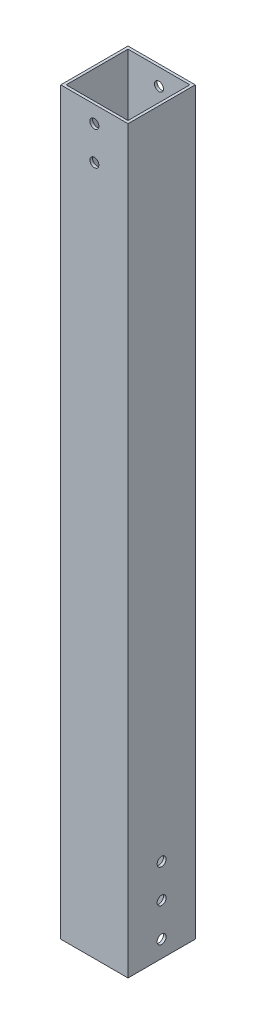
SolidWorks part; units mm, degrees
material "6061 Alloy"
ref_plane "Front Plane" through (0, 0, 0) normal (0, 0, 1) x (1, 0, 0)
ref_plane "Top Plane" through (0, 0, 0) normal (0, 1, 0) x (1, 0, 0)
ref_plane "Right Plane" through (0, 0, 0) normal (1, 0, 0) x (0, 0, -1)
sketch "Sketch1" plane through (0, 0, 0) normal (0, 1, 0) x (1, 0, 0)
  line L1 (19.05, 19.05) -> (-19.05, 19.05)
  line L2 (19.05, 19.05) -> (19.05, -19.05)
  line L3 (19.05, -19.05) -> (-19.05, -19.05)
  line L4 (-19.05, 19.05) -> (-19.05, -19.05)
  line L5 (19.05, 19.05) -> (-19.05, -19.05) construction
  line L6 (19.05, -19.05) -> (-19.05, 19.05) construction
  point P0 (0, 0)
  dimension "D1" = 38.1
extrude "Extrude-Thin1" add sketch "Sketch1" along normal blind 419.1 thin thin type one direction reverse wall 1.524
sketch "Sketch2" plane through (19.05, 0, 0) normal (1, 0, 0) x (0, 0, -1)
  line L0 (-19.05, 0) -> (19.05, 0) construction
  circle A0 centre (0, 9.525) radius 2.54
  circle A1 centre (0, 28.575) radius 2.54
  circle A2 centre (0, 47.625) radius 2.54
  point P7 (0, 0)
  dimension "D1" = 5.08
  dimension "D4" = 19.05
  dimension "D2" = 9.525
  dimension "D3" = 28.575
hole_wizard "#10 Clearance Hole1" positions "Sketch3" profile "Sketch4" hole size "#10" standard "ANSI Inch" end condition through all
sketch "Sketch3" plane through (19.05, 0, 0) normal (1, 0, 0) x (0, 0, -1)
  point P0 (0, 9.525)
  point P3 (0, 28.575)
  point P6 (0, 47.625)
sketch "Sketch4" plane through (19.05, 9.525, 0) normal (0, 1, 0) x (0, 0, -1)
  line L0 (0, 0) -> (0, 38.1)
  line L1 (0, 38.1) -> (2.5527, 38.1)
  line L2 (2.5527, 38.1) -> (2.5527, 0)
  line L5 (2.5527, 0) -> (0, 0)
  line L11 (0, -6.35) -> (0, 107.95) construction
  dimension "Thru Hole Dia." = 5.1054
  dimension "Thru Hole Depth" = 38.1
sketch "Sketch5" plane through (0, 0, 19.05) normal (0, 0, 1) x (1, 0, 0)
  line L0 (-19.05, 419.1) -> (19.05, 419.1) construction
  circle A0 centre (0, 409.575) radius 2.54
  circle A1 centre (0, 390.525) radius 2.54
  point P7 (0, 0)
  point P8 (0, 0)
  dimension "D1" = 5.08
  dimension "D2" = 9.525
  dimension "D3" = 28.575
hole_wizard "#10 Clearance Hole2" positions "Sketch6" profile "Sketch7" hole size "#10" standard "ANSI Inch" end condition through all
sketch "Sketch6" plane through (0, 0, 19.05) normal (0, 0, 1) x (1, 0, 0)
  point P0 (0, 390.525)
  point P3 (0, 409.575)
sketch "Sketch7" plane through (0, 390.525, 19.05) normal (1, 0, 0) x (0, -1, 0)
  line L0 (0, 0) -> (0, 38.1)
  line L1 (0, 38.1) -> (2.5527, 38.1)
  line L2 (2.5527, 38.1) -> (2.5527, 0)
  line L5 (2.5527, 0) -> (0, 0)
  line L11 (0, -6.35) -> (0, 107.95) construction
  dimension "Thru Hole Dia." = 5.1054
  dimension "Thru Hole Depth" = 38.1
